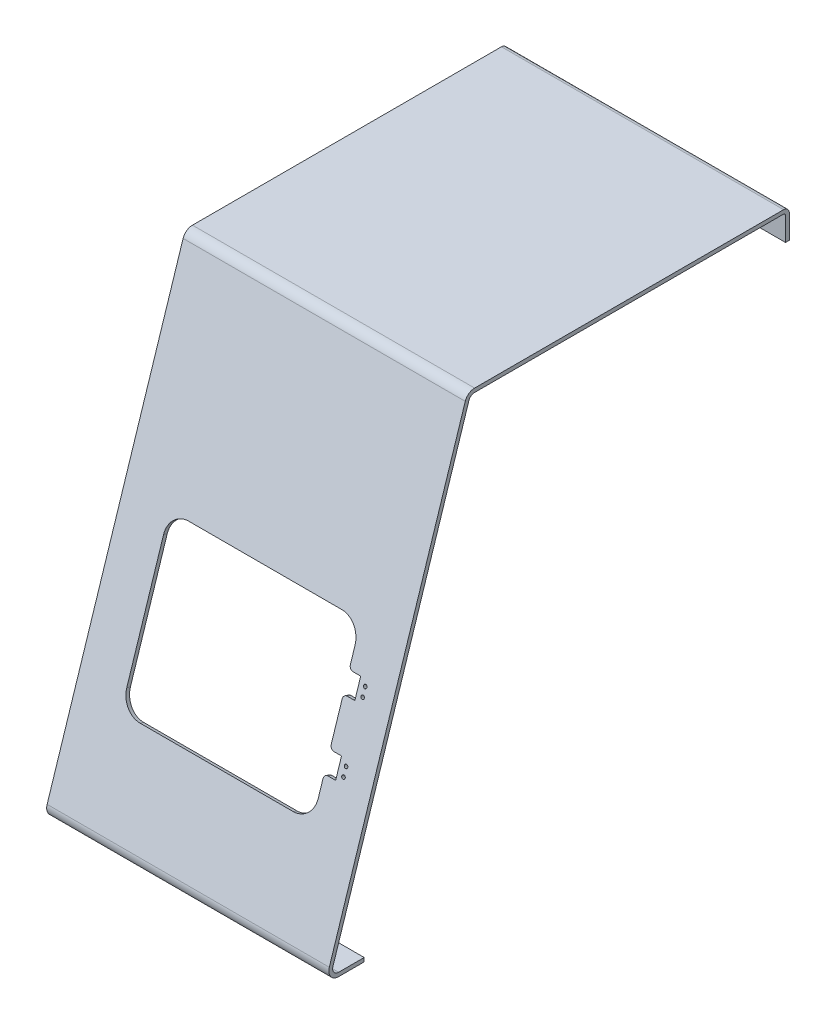
SolidWorks part; units mm, degrees
ref_plane "Front Plane" through (0, 0, 0) normal (0, 0, 1) x (1, 0, 0)
ref_plane "Top Plane" through (0, 0, 0) normal (0, 1, 0) x (1, 0, 0)
ref_plane "Right Plane" through (0, 0, 0) normal (1, 0, 0) x (0, 0, -1)
sketch "Sketch1" plane through (0, 0, 0) normal (1, 0, 0) x (0, 0, -1)
  line L0 (122.5, 310) -> (122.5, 328.5)
  line L1 (121, 330) -> (-121.0014, 330)
  line L2 (-125.4686, 326.7458) -> (-231.9672, -3.8678)
  line L3 (-227.5, -10) -> (-207.5, -10)
  arc A0 (-231.9672, -3.8678) -> (-227.5, -10) centre (-227.5, -5.3068) ccw
  arc A1 (-121.0014, 330) -> (-125.4686, 326.7458) centre (-121.0014, 325.3068) ccw
  arc A2 (122.5, 328.5) -> (121, 330) centre (121, 328.5) ccw
  dimension "D1" = 1.5
  dimension "D3" = 20
extrude "Extrude-Thin1" add sketch "Sketch1" along normal mid plane 221 thin thin type one direction wall 3
sketch "Sketch2" plane through (0, 68.2539, 211.8868) normal (0, 0.3066, 0.9518) x (1, 0, 0)
  line L0 (0, -82.1274) -> (0, -2.1274) construction
  line L1 (-60, 121.8726) -> (60, 121.8726)
  line L2 (-75, 106.8726) -> (-75, 12.8726)
  line L3 (-60, -2.1274) -> (60, -2.1274)
  line L4 (75, 106.8726) -> (75, 94.8726)
  line L5 (75, 73.8726) -> (75, 45.8726)
  line L6 (110.5, -82.1274) -> (-110.5, -82.1274) construction
  line L7 (75, 24.8726) -> (75, 12.8726)
  line L8 (78, 91.8726) -> (84, 91.8726)
  line L10 (78, 76.8726) -> (84, 76.8726)
  line L11 (84, 91.8726) -> (84, 76.8726)
  line L12 (78, 42.8726) -> (84, 42.8726)
  line L14 (78, 27.8726) -> (84, 27.8726)
  line L15 (84, 42.8726) -> (84, 27.8726)
  line L16 (88.85, 87.6726) -> (88.85, 81.0726) construction
  line L17 (88.85, 84.3726) -> (84, 84.3726) construction
  line L18 (75, 59.8726) -> (84, 59.8726) construction
  arc A0 (-75, 12.8726) -> (-60, -2.1274) centre (-60, 12.8726) ccw
  arc A1 (60, -2.1274) -> (75, 12.8726) centre (60, 12.8726) ccw
  arc A2 (60, 121.8726) -> (75, 106.8726) centre (60, 106.8726) cw
  arc A3 (-60, 121.8726) -> (-75, 106.8726) centre (-60, 106.8726) ccw
  arc A4 (75, 24.8726) -> (78, 27.8726) centre (78, 24.8726) cw
  arc A5 (78, 42.8726) -> (75, 45.8726) centre (78, 45.8726) cw
  arc A6 (75, 73.8726) -> (78, 76.8726) centre (78, 73.8726) cw
  arc A7 (78, 91.8726) -> (75, 94.8726) centre (78, 94.8726) cw
  circle A8 centre (88.85, 87.6726) radius 1.35
  circle A9 centre (88.85, 81.0726) radius 1.35
  circle A10 centre (88.85, 38.6726) radius 1.35
  circle A11 centre (88.85, 32.0726) radius 1.35
  point P13 (-75, -2.1274)
  point P16 (75, -2.1274)
  point P19 (75, 121.8726)
  point P35 (75, 91.8726)
  dimension "D4" = 15
  dimension "D9" = 3
  dimension "D10" = 2.7
  dimension "D11" = 3.9
  dimension "D12" = 3.5
  dimension "D1" = 150
  dimension "D2" = 124
  dimension "D3" = 80
  dimension "D5" = 15
  dimension "D6" = 9
  dimension "D7" = 15
  dimension "D8" = 15
extrude "Cut-Extrude1" cut sketch "Sketch2" against normal up to next
